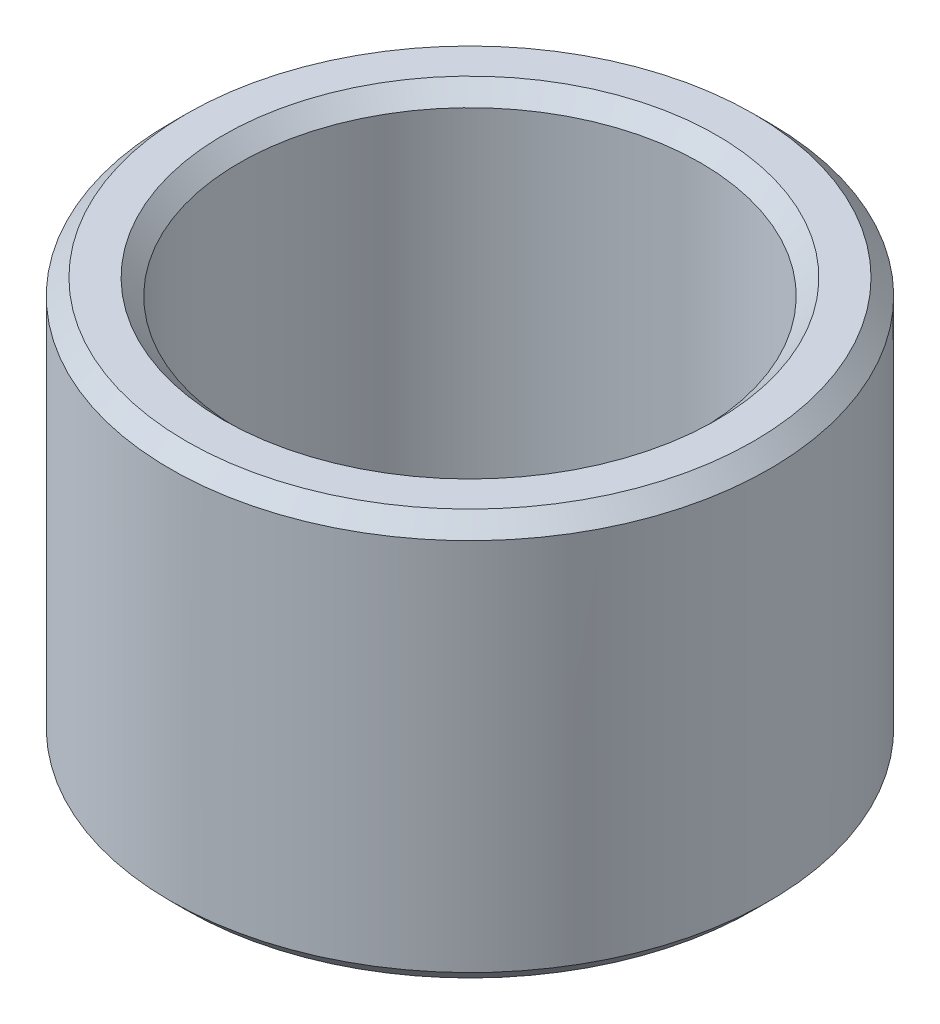
SolidWorks part; units mm, degrees
ref_plane "Front Plane" through (0, 0, 0) normal (0, 0, 1) x (1, 0, 0)
ref_plane "Top Plane" through (0, 0, 0) normal (0, 1, 0) x (1, 0, 0)
ref_plane "Right Plane" through (0, 0, 0) normal (1, 0, 0) x (0, 0, -1)
sketch "Sketch1" plane through (0, 0, 0) normal (0, 1, 0) x (1, 0, 0)
  circle A0 centre (0, 0) radius 35
  dimension "SLEEVE_OD" = 70
extrude "Boss-Extrude1" add sketch "Sketch1" along normal blind 47.4337
sketch "Sketch2" plane through (0, 0, 0) normal (0, 1, 0) x (1, 0, 0)
  circle A0 centre (0, 0) radius 26.9491
  dimension "BORE_D" = 53.8982
extrude "Cut-Extrude1" cut sketch "Sketch2" along normal through all
chamfer "Chamfer1" distance 1.8715 angle 45 4 edges at (0, 47.4337, 26.9491) (0, 0, 26.9491) (0, 0, 35) (0, 47.4337, 35)
